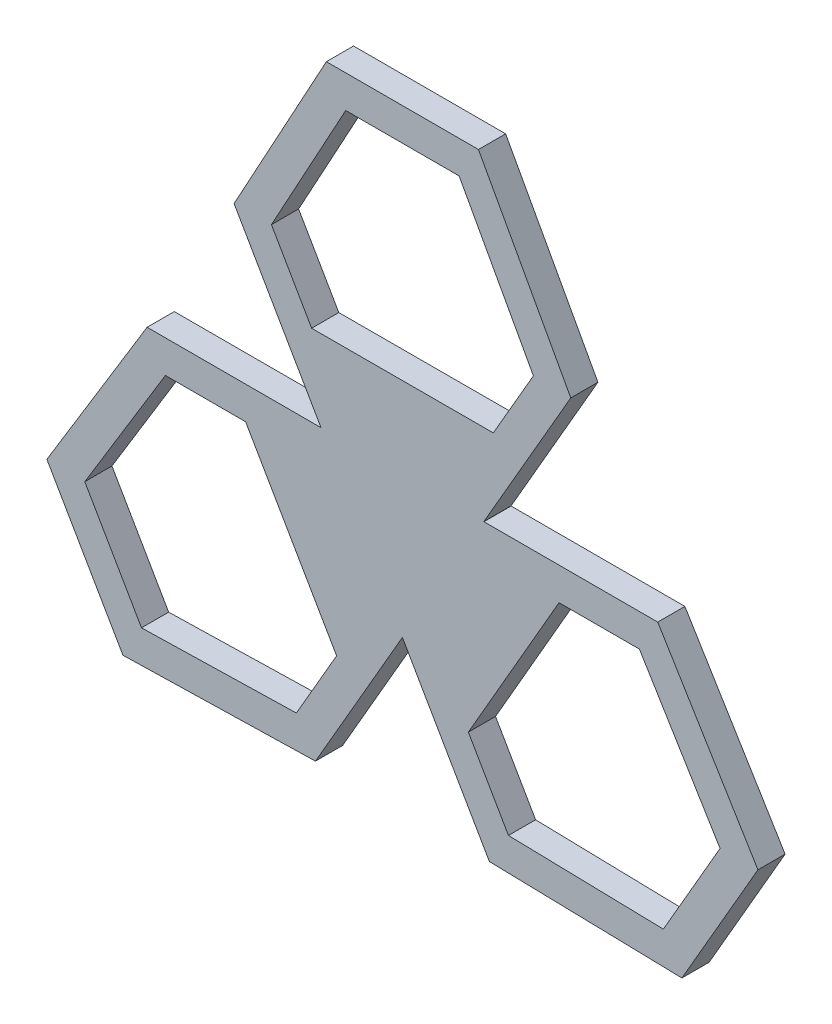
SolidWorks part; units mm, degrees
ref_plane "Front Plane" through (0, 0, 0) normal (0, 0, 1) x (1, 0, 0)
ref_plane "Top Plane" through (0, 0, 0) normal (0, 1, 0) x (1, 0, 0)
ref_plane "Right Plane" through (0, 0, 0) normal (1, 0, 0) x (0, 0, -1)
sketch "Sketch1" plane through (0, 0, 0) normal (0, 0, 1) x (1, 0, 0)
  line L0 (0, 17.3205) -> (0, 67.5) construction
  line L1 (15, 8.6603) -> (10, 17.3205) construction
  line L2 (0, 17.3205) -> (-10, 17.3205) construction
  line L3 (-15, 8.6603) -> (-20, 0) construction
  line L4 (-20, 0) -> (-15, -8.6603) construction
  line L5 (-10, -17.3205) -> (0, -17.3205) construction
  line L6 (15, -8.6603) -> (20, 0) construction
  line L7 (77.9423, 0) -> (38.9711, 67.5) construction
  line L8 (38.9711, 67.5) -> (-38.9711, 67.5) construction
  line L9 (-38.9711, 67.5) -> (-77.9423, 0) construction
  line L10 (-77.9423, 0) -> (-38.9711, -67.5) construction
  line L11 (-38.9711, -67.5) -> (38.9711, -67.5) construction
  line L12 (38.9711, -67.5) -> (77.9423, 0) construction
  line L14 (-30.995, 36.3817) -> (-14, 67.5)
  line L18 (10, 17.3205) -> (0, 17.3205) construction
  line L19 (-15, -8.6603) -> (-10, -17.3205) construction
  line L20 (10, -17.3205) -> (15, -8.6603) construction
  line L21 (-10, 17.3205) -> (-15, 8.6603) construction
  line L22 (20, 0) -> (15, 8.6603) construction
  line L23 (0, -17.3205) -> (10, -17.3205) construction
  line L24 (-10, 17.3205) -> (-14.995, 8.6689) construction
  line L25 (-15, 8.6603) -> (-14.995, 8.6689)
  line L26 (-14.995, 8.6689) -> (-30.995, 36.3817)
  line L27 (14, 67.5) -> (-14, 67.5)
  line L28 (30.995, 36.3817) -> (14, 67.5)
  line L29 (14.995, 8.6689) -> (30.995, 36.3817)
  line L30 (15, 8.6603) -> (14.995, 8.6689)
  line L31 (15, 8.6603) -> (15.005, 8.6516)
  line L32 (15.005, 8.6516) -> (47.005, 8.6516)
  line L33 (47.005, 8.6516) -> (65.4567, -21.6256)
  line L34 (51.4567, -45.8744) -> (65.4567, -21.6256)
  line L35 (16.01, -45.0333) -> (51.4567, -45.8744)
  line L36 (0.01, -17.3205) -> (16.01, -45.0333)
  line L37 (0, -17.3205) -> (0.01, -17.3205)
  line L38 (0, -17.3205) -> (-0.01, -17.3205)
  line L39 (-0.01, -17.3205) -> (-16.01, -45.0333)
  line L40 (-16.01, -45.0333) -> (-51.4567, -45.8744)
  line L41 (-65.4567, -21.6256) -> (-51.4567, -45.8744)
  line L42 (-47.005, 8.6516) -> (-65.4567, -21.6256)
  line L43 (-15.005, 8.6516) -> (-47.005, 8.6516)
  line L44 (-15, 8.6603) -> (-15.005, 8.6516)
  arc A0 (15, 8.6603) -> (0, 17.3205) centre (0, 0) ccw construction
  circle A1 centre (0, 0) radius 67.5 construction
  arc A2 (15, -8.6603) -> (15, 8.6603) centre (0, 0) ccw construction
  arc A3 (0, -17.3205) -> (15, -8.6603) centre (0, 0) ccw construction
  arc A4 (0, 17.3205) -> (-15, 8.6603) centre (0, 0) ccw construction
  arc A5 (-15, -8.6603) -> (0, -17.3205) centre (0, 0) ccw construction
  arc A6 (-15, 8.6603) -> (-15, -8.6603) centre (0, 0) ccw construction
  point P47 (0, 0)
  dimension "D1" = 20
  dimension "D2" = 135
  dimension "D3" = 14
  dimension "D4" = 9.99
  dimension "D5" = 32
  dimension "D6" = 120
  dimension "D7" = 3
extrude "Boss-Extrude1" add sketch "Sketch1" along normal blind 5
sketch "Sketch2" plane through (0, 0, 5) normal (0, 0, 1) x (1, 0, 0)
  line L0 (-15.005, 8.6516) -> (0.01, -17.3205) construction
  line L1 (-20.4956, -11.8211) -> (-7.4975, -4.3345) construction
  line L2 (-15.005, 8.6516) -> (15.005, 8.6516) construction
  line L3 (15.005, 8.6516) -> (0.01, -17.3205) construction
  line L5 (-28.8721, 2.6516) -> (-12.119, -26.2939)
  line L20 (-19.5212, -39.1149) -> (-5.2062, -14.3205)
  line L21 (-48.0404, -39.7916) -> (-19.5212, -39.1149)
  line L22 (-58.4807, -21.7084) -> (-48.0404, -39.7916)
  line L23 (-43.6351, 2.6516) -> (-58.4807, -21.7084)
  line L24 (-15.005, 2.6516) -> (-43.6351, 2.6516)
  line L25 (-19.5212, -39.1149) -> (-12.119, -26.2939)
  line L26 (-48.0404, -39.7916) -> (-19.5212, -39.1149)
  line L27 (-58.4807, -21.7084) -> (-48.0404, -39.7916)
  line L28 (-43.6351, 2.6516) -> (-58.4807, -21.7084)
  line L29 (-28.8721, 2.6516) -> (-43.6351, 2.6516)
  line L31 (-24.1139, 36.4633) -> (-16.7117, 23.6423)
  line L32 (16.7324, 23.6782) -> (-16.7117, 23.6423)
  line L33 (16.7324, 23.6782) -> (24.1139, 36.4633)
  line L34 (24.1139, 36.4633) -> (10.4404, 61.5)
  line L35 (10.4404, 61.5) -> (-10.4404, 61.5)
  line L36 (-10.4404, 61.5) -> (-24.1139, 36.4633)
  line L37 (43.6351, 2.6516) -> (28.8306, 2.6516)
  line L38 (12.1397, -26.3298) -> (28.8306, 2.6516)
  line L39 (12.1397, -26.3298) -> (19.5212, -39.1149)
  line L40 (19.5212, -39.1149) -> (48.0404, -39.7916)
  line L41 (48.0404, -39.7916) -> (58.4807, -21.7084)
  line L42 (58.4807, -21.7084) -> (43.6351, 2.6516)
  point P31 (0, -1.1576)
  point P32 (0, 0)
  dimension "D2" = 15
  dimension "D1" = 6
  dimension "D3" = 3
extrude "Cut-Extrude1" cut sketch "Sketch2" against normal through all
